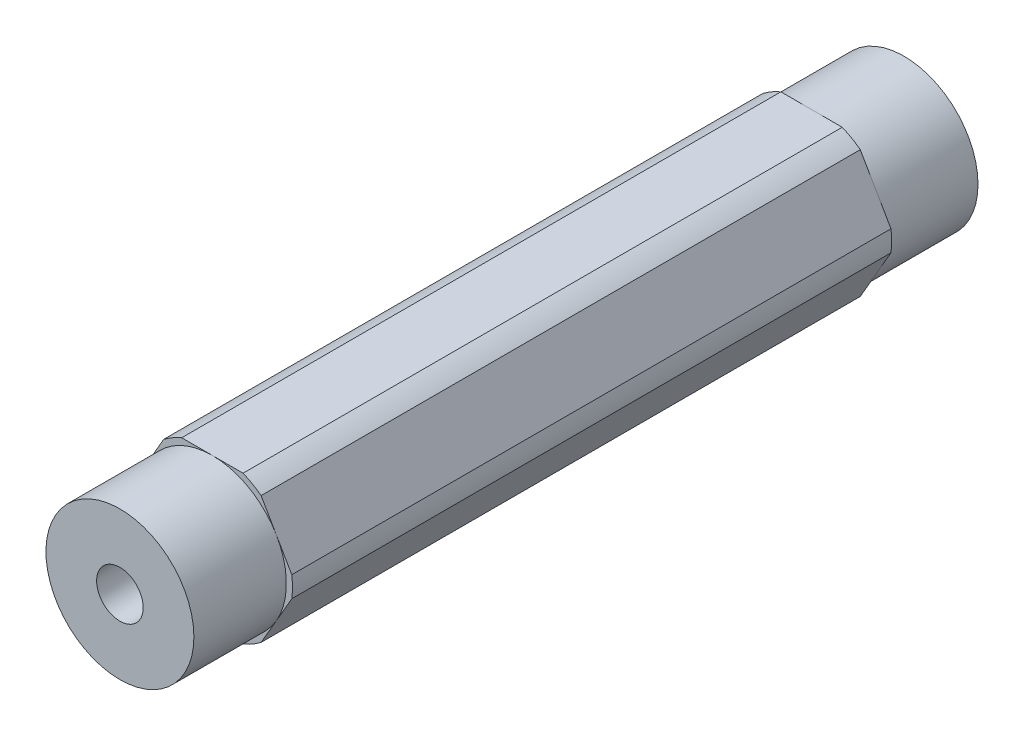
SolidWorks part; units mm, degrees
material "6061-T6 (SS)"
ref_plane "Front Plane" through (0, 0, 0) normal (0, 0, 1) x (1, 0, 0)
ref_plane "Top Plane" through (0, 0, 0) normal (0, 1, 0) x (1, 0, 0)
ref_plane "Right Plane" through (0, 0, 0) normal (1, 0, 0) x (0, 0, -1)
sketch "Sketch1" plane through (0, 0, 0) normal (0, 0, 1) x (1, 0, 0)
  line L1 (3.6662, 6.35) -> (-3.6662, 6.35)
  line L2 (-3.6662, 6.35) -> (-7.3323, 0)
  line L3 (-7.3323, 0) -> (-3.6662, -6.35)
  line L4 (-3.6662, -6.35) -> (3.6662, -6.35)
  line L5 (3.6662, -6.35) -> (7.3323, 0)
  line L6 (7.3323, 0) -> (3.6662, 6.35)
  circle A0 centre (0, 0) radius 6.35 construction
  circle A1 centre (0, 0) radius 2
  circle A2 centre (0, 0) radius 6.875
  point P1 (0, 6.35)
  dimension "D2" = 13.75
  dimension "D3" = 4
  dimension "D1" = 12.7
extrude "Boss-Extrude1" add sketch "Sketch1" along normal mid plane 51.435 contours L6 A2 L1 L2 L3 L4 L5 A1 region at (3.3439, 5.7918, 0)
sketch "Sketch4" plane through (0, 0, 25.7175) normal (0, 0, 1) x (1, 0, 0)
  circle A0 centre (0, 0) radius 6.35
  circle A1 centre (0, 0) radius 2 construction
  circle A2 centre (0, 0) radius 2
  dimension "D1" = 12.7
extrude "Boss-Extrude2" add sketch "Sketch4" along normal blind 7.9375
mirror "Mirror1" about plane through (0, 0, 0) normal (0, 0, 1) of "Boss-Extrude2"
equation "\"D2@Sketch1\"=13.75mm"
equation "\"D3@Sketch1\"=4mm"
